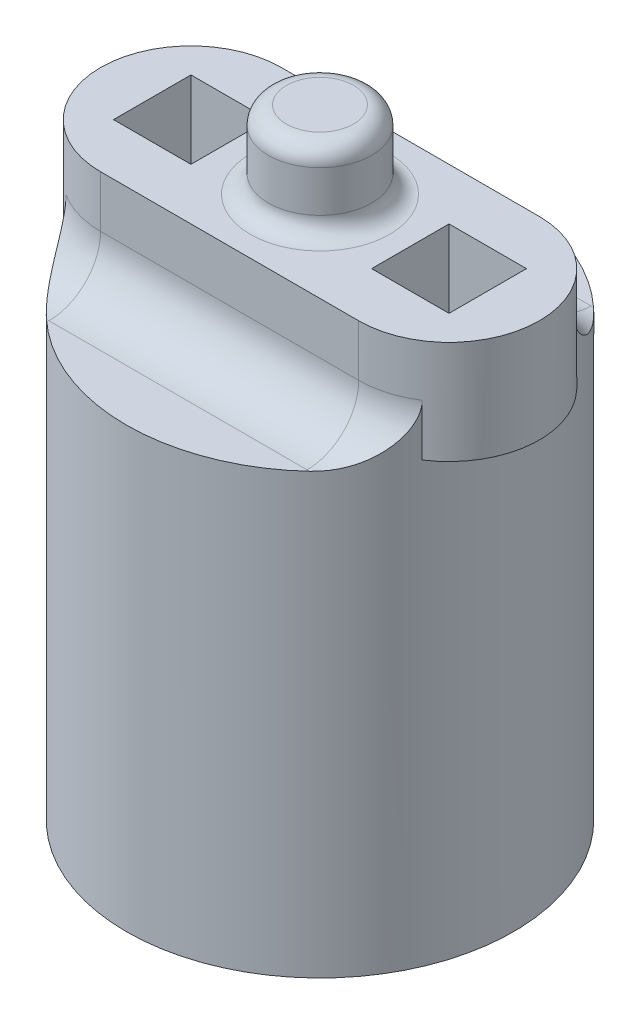
SolidWorks part; units mm, degrees
ref_plane "Front Plane" through (0, 0, 0) normal (0, 0, 1) x (1, 0, 0)
ref_plane "Top Plane" through (0, 0, 0) normal (0, 1, 0) x (1, 0, 0)
ref_plane "Right Plane" through (0, 0, 0) normal (1, 0, 0) x (0, 0, -1)
sketch "Sketch1" plane through (0, 0, 0) normal (0, 1, 0) x (1, 0, 0)
  circle A0 centre (0, 0) radius 7.5
  circle A1 centre (0, 0) radius 2.575
  dimension "D1" = 15
  dimension "D2" = 5.15
extrude "Boss-Extrude1" add sketch "Sketch1" along normal blind 15
sketch "Sketch2" plane through (0, 0, 0) normal (0, 0, 1) x (1, 0, 0)
  line L1 (0, 7.5) -> (0, 15) construction
  line L2 (0, 7.5) -> (0, 0) construction
  circle A0 centre (0, 7.5) radius 1.25
  dimension "D1" = 2.5
extrude "Cut-Extrude1" cut sketch "Sketch2" against normal through all contours A0
ref_plane "Plane1" through (0, 0, -7.5) normal (0, 0, -1) x (-1, 0, 0)
thread "Thread1" pitch 0.5 method cut profile "Thread Profile1" start angle 0, offset 1, length 7, pitch 0.5, diameter 2.5
ref_plane "Plane2" through (1.25, 7.5, -8.5) normal (0, -1, 0) x (1, 0, 0)
sketch "Thread Profile1" plane through (1.25, 7.5, -8.5) normal (0, -1, 0) x (1, 0, 0)
  line L0 (0, 0) -> (0, 0.5) construction
  line L1 (0, 0) -> (0.2706, 0.1562)
  line L2 (0.2706, 0.1562) -> (0.2706, 0.2187)
  line L3 (0.2706, 0.2187) -> (0, 0.375)
  line L4 (0.2706, 0.1875) -> (0, 0.1875) construction
  line L11 (0, 0) -> (0, 0.375)
  point P2 (0, 0)
  dimension "Pitch" = 0.5
  dimension "Profile_Angle" = 60
  dimension "Profile_Land" = 0.0625
  dimension "Profile_Height" = 0.2706
sketch "Sketch12" plane through (0, 15, 0) normal (0, 1, 0) x (1, 0, 0)
  circle A0 centre (0, 0) radius 7.5
extrude "Boss-Extrude3" add sketch "Sketch12" along normal blind 2
sketch "Sketch5" plane through (0, 0, -7.5) normal (0, 0, -1) x (-1, 0, 0)
  circle A0 centre (0, 7.5) radius 1.75
  dimension "D1" = 3.5
extrude "Cut-Extrude2" cut sketch "Sketch5" against normal blind 10 draft 45
sketch "Sketch10" plane through (0, 17, 0) normal (0, 1, 0) x (1, 0, 0)
  circle A0 centre (0, 0) radius 7.5
sketch "Sketch11" plane through (0, 17, 0) normal (0, 1, 0) x (1, 0, 0)
  line L0 (-5, 0) -> (5, 0) construction
  line L1 (-6.5, 1.5) -> (-3.5, 1.5)
  line L2 (-6.5, 1.5) -> (-6.5, -1.5)
  line L3 (-6.5, -1.5) -> (-3.5, -1.5)
  line L4 (-3.5, 1.5) -> (-3.5, -1.5)
  line L5 (-6.5, 1.5) -> (-3.5, -1.5) construction
  line L6 (-6.5, -1.5) -> (-3.5, 1.5) construction
  line L7 (3.5, 1.5) -> (6.5, 1.5)
  line L8 (3.5, 1.5) -> (3.5, -1.5)
  line L9 (3.5, -1.5) -> (6.5, -1.5)
  line L10 (6.5, 1.5) -> (6.5, -1.5)
  line L11 (3.5, 1.5) -> (6.5, -1.5) construction
  line L12 (3.5, -1.5) -> (6.5, 1.5) construction
  line L13 (-5, 3.5) -> (5, 3.5)
  line L14 (-5, -3.5) -> (5, -3.5)
  arc A0 (-5, 3.5) -> (-5, -3.5) centre (-5, 0) ccw
  arc A1 (5, -3.5) -> (5, 3.5) centre (5, 0) ccw
  point P0 (-5, 0)
  point P5 (5, 0)
  point P12 (0, 0)
  dimension "D4" = 5
  dimension "D1" = 3
  dimension "D2" = 3
  dimension "D3" = 0
  dimension "D5" = 3
  dimension "D6" = 5
extrude "Boss-Extrude2" add sketch "Sketch11" along normal blind 4
sketch "Sketch13" plane through (0, 21, 0) normal (0, 1, 0) x (1, 0, 0)
  circle A0 centre (0, 0) radius 2
  dimension "D1" = 4
extrude "Boss-Extrude4" add sketch "Sketch13" along normal blind 3
fillet "Fillet1" radius 0.7 2 edges at (0, 24, 2) (0, 21, 2)
fillet "Fillet2" radius 2 6 edges at (5.9905, 17, -3.3569) (0, 17, -3.5) (-5.9905, 17, 3.3569) (5.9905, 17, 3.3569) (-5.9905, 17, -3.3569) (0, 17, 3.5)
